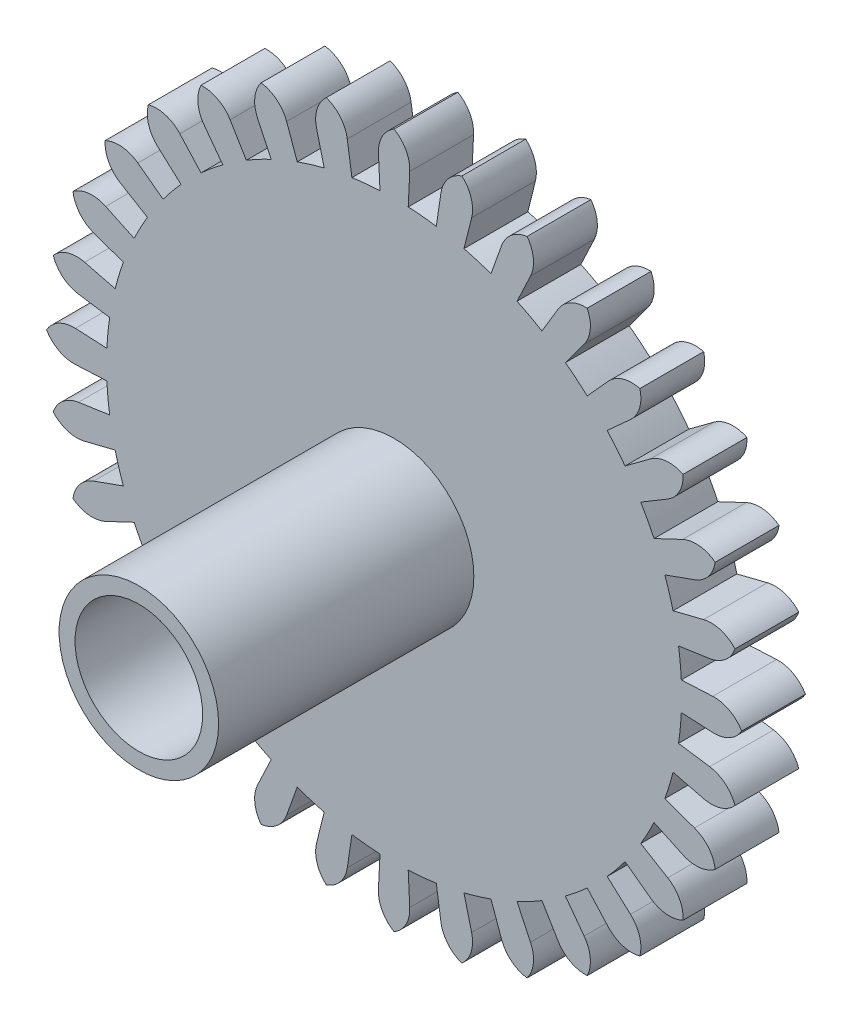
SolidWorks part; units mm, degrees
material "AISI 347 Annealed Stainless Steel (SS)"
ref_plane "Front Plane" through (0, 0, 0) normal (0, 0, 1) x (1, 0, 0)
ref_plane "Top Plane" through (0, 0, 0) normal (0, 1, 0) x (1, 0, 0)
ref_plane "Right Plane" through (0, 0, 0) normal (1, 0, 0) x (0, 0, -1)
sketch "Sketch2" plane through (0, 0, 0) normal (0, 0, 1) x (1, 0, 0)
  line L0 (0, 0) -> (0, 5.2279) construction
  line L1 (-0.1769, 3.6007) -> (-0.1963, 3.9952)
  line L2 (0.1769, 3.6007) -> (0.1963, 3.9952)
  line L3 (0.5289, 3.566) -> (0.5869, 3.9567)
  line L4 (0.876, 3.497) -> (0.9719, 3.8801)
  line L5 (1.2145, 3.3943) -> (1.3475, 3.7662)
  line L6 (1.5414, 3.2589) -> (1.7102, 3.6159)
  line L7 (1.8533, 3.0921) -> (2.0564, 3.4309)
  line L8 (2.1475, 2.8956) -> (2.3828, 3.2128)
  line L9 (2.421, 2.6711) -> (2.6862, 2.9638)
  line L10 (2.6711, 2.421) -> (2.9638, 2.6862)
  line L11 (2.8956, 2.1475) -> (3.2128, 2.3828)
  line L12 (3.0921, 1.8533) -> (3.4309, 2.0564)
  line L13 (3.2589, 1.5414) -> (3.6159, 1.7102)
  line L14 (3.3943, 1.2145) -> (3.7662, 1.3475)
  line L15 (3.497, 0.876) -> (3.8801, 0.9719)
  line L16 (3.566, 0.5289) -> (3.9567, 0.5869)
  line L17 (3.6007, 0.1769) -> (3.9952, 0.1963)
  line L18 (3.6007, -0.1769) -> (3.9952, -0.1963)
  line L19 (3.566, -0.5289) -> (3.9567, -0.5869)
  line L20 (3.497, -0.876) -> (3.8801, -0.9719)
  line L21 (3.3943, -1.2145) -> (3.7662, -1.3475)
  line L22 (3.2589, -1.5414) -> (3.6159, -1.7102)
  line L23 (3.0921, -1.8533) -> (3.4309, -2.0564)
  line L24 (2.8956, -2.1475) -> (3.2128, -2.3828)
  line L25 (2.6711, -2.421) -> (2.9638, -2.6862)
  line L26 (2.421, -2.6711) -> (2.6862, -2.9638)
  line L27 (2.1475, -2.8956) -> (2.3828, -3.2128)
  line L28 (1.8533, -3.0921) -> (2.0564, -3.4309)
  line L29 (1.5414, -3.2589) -> (1.7102, -3.6159)
  line L30 (1.2145, -3.3943) -> (1.3475, -3.7662)
  line L31 (0.876, -3.497) -> (0.9719, -3.8801)
  line L32 (0.5289, -3.566) -> (0.5869, -3.9567)
  line L33 (0.1769, -3.6007) -> (0.1963, -3.9952)
  line L34 (-0.1769, -3.6007) -> (-0.1963, -3.9952)
  line L35 (-0.5289, -3.566) -> (-0.5869, -3.9567)
  line L36 (-0.876, -3.497) -> (-0.9719, -3.8801)
  line L37 (-1.2145, -3.3943) -> (-1.3475, -3.7662)
  line L38 (-1.5414, -3.2589) -> (-1.7102, -3.6159)
  line L39 (-1.8533, -3.0921) -> (-2.0564, -3.4309)
  line L40 (-2.1475, -2.8956) -> (-2.3828, -3.2128)
  line L41 (-2.421, -2.6711) -> (-2.6862, -2.9638)
  line L42 (-2.6711, -2.421) -> (-2.9638, -2.6862)
  line L43 (-2.8956, -2.1475) -> (-3.2128, -2.3828)
  line L44 (-3.0921, -1.8533) -> (-3.4309, -2.0564)
  line L45 (-3.2589, -1.5414) -> (-3.6159, -1.7102)
  line L46 (-3.3943, -1.2145) -> (-3.7662, -1.3475)
  line L47 (-3.497, -0.876) -> (-3.8801, -0.9719)
  line L48 (-3.566, -0.5289) -> (-3.9567, -0.5869)
  line L49 (-3.6007, -0.1769) -> (-3.9952, -0.1963)
  line L50 (-3.6007, 0.1769) -> (-3.9952, 0.1963)
  line L51 (-3.566, 0.5289) -> (-3.9567, 0.5869)
  line L52 (-3.497, 0.876) -> (-3.8801, 0.9719)
  line L53 (-3.3943, 1.2145) -> (-3.7662, 1.3475)
  line L54 (-3.2589, 1.5414) -> (-3.6159, 1.7102)
  line L55 (-3.0921, 1.8533) -> (-3.4309, 2.0564)
  line L56 (-2.8956, 2.1475) -> (-3.2128, 2.3828)
  line L57 (-2.6711, 2.421) -> (-2.9638, 2.6862)
  line L58 (-2.421, 2.6711) -> (-2.6862, 2.9638)
  line L59 (-2.1475, 2.8956) -> (-2.3828, 3.2128)
  line L60 (-1.8533, 3.0921) -> (-2.0564, 3.4309)
  line L61 (-1.5414, 3.2589) -> (-1.7102, 3.6159)
  line L62 (-1.2145, 3.3943) -> (-1.3475, 3.7662)
  line L63 (-0.876, 3.497) -> (-0.9719, 3.8801)
  line L64 (-0.5289, 3.566) -> (-0.5869, 3.9567)
  arc A0 (0.5289, 3.566) -> (0.1769, 3.6007) centre (0, 0) ccw
  arc A1 (-0.1769, 3.6007) -> (-0.5289, 3.566) centre (0, 0) ccw
  arc A2 (1.2145, 3.3943) -> (0.876, 3.497) centre (0, 0) ccw
  arc A3 (0.1963, 3.9952) -> (0, 4.3574) centre (-0.2002, 4.0147) ccw
  arc A4 (-0.1963, 3.9952) -> (0, 4.3574) centre (0.2002, 4.0147) cw
  arc A5 (0.9719, 3.8801) -> (0.8501, 4.2737) centre (0.5869, 3.9766) ccw
  arc A6 (0.5869, 3.9567) -> (0.8501, 4.2737) centre (0.9795, 3.8985) cw
  arc A7 (1.7102, 3.6159) -> (1.6675, 4.0257) centre (1.3514, 3.7857) ccw
  arc A8 (1.3475, 3.7662) -> (1.6675, 4.0257) centre (1.7213, 3.6325) cw
  arc A9 (2.3828, 3.2128) -> (2.4209, 3.6231) centre (2.064, 3.4493) ccw
  arc A10 (2.0564, 3.4309) -> (2.4209, 3.6231) centre (2.3969, 3.2269) cw
  arc A11 (2.9638, 2.6862) -> (3.0812, 3.0812) centre (2.6973, 2.9803) ccw
  arc A12 (2.6862, 2.9638) -> (3.0812, 3.0812) centre (2.9803, 2.6973) cw
  arc A13 (3.4309, 2.0564) -> (3.6231, 2.4209) centre (3.2269, 2.3969) ccw
  arc A14 (3.2128, 2.3828) -> (3.6231, 2.4209) centre (3.4493, 2.064) cw
  arc A15 (3.7662, 1.3475) -> (4.0257, 1.6675) centre (3.6325, 1.7213) ccw
  arc A16 (3.6159, 1.7102) -> (4.0257, 1.6675) centre (3.7857, 1.3514) cw
  arc A17 (3.9567, 0.5869) -> (4.2737, 0.8501) centre (3.8985, 0.9795) ccw
  arc A18 (3.8801, 0.9719) -> (4.2737, 0.8501) centre (3.9766, 0.5869) cw
  arc A19 (3.9952, -0.1963) -> (4.3574, 0) centre (4.0147, 0.2002) ccw
  arc A20 (3.9952, 0.1963) -> (4.3574, 0) centre (4.0147, -0.2002) cw
  arc A21 (3.8801, -0.9719) -> (4.2737, -0.8501) centre (3.9766, -0.5869) ccw
  arc A22 (3.9567, -0.5869) -> (4.2737, -0.8501) centre (3.8985, -0.9795) cw
  arc A23 (3.6159, -1.7102) -> (4.0257, -1.6675) centre (3.7857, -1.3514) ccw
  arc A24 (3.7662, -1.3475) -> (4.0257, -1.6675) centre (3.6325, -1.7213) cw
  arc A25 (3.2128, -2.3828) -> (3.6231, -2.4209) centre (3.4493, -2.064) ccw
  arc A26 (3.4309, -2.0564) -> (3.6231, -2.4209) centre (3.2269, -2.3969) cw
  arc A27 (2.6862, -2.9638) -> (3.0812, -3.0812) centre (2.9803, -2.6973) ccw
  arc A28 (2.9638, -2.6862) -> (3.0812, -3.0812) centre (2.6973, -2.9803) cw
  arc A29 (2.0564, -3.4309) -> (2.4209, -3.6231) centre (2.3969, -3.2269) ccw
  arc A30 (2.3828, -3.2128) -> (2.4209, -3.6231) centre (2.064, -3.4493) cw
  arc A31 (1.3475, -3.7662) -> (1.6675, -4.0257) centre (1.7213, -3.6325) ccw
  arc A32 (1.7102, -3.6159) -> (1.6675, -4.0257) centre (1.3514, -3.7857) cw
  arc A33 (0.5869, -3.9567) -> (0.8501, -4.2737) centre (0.9795, -3.8985) ccw
  arc A34 (0.9719, -3.8801) -> (0.8501, -4.2737) centre (0.5869, -3.9766) cw
  arc A35 (-0.1963, -3.9952) -> (0, -4.3574) centre (0.2002, -4.0147) ccw
  arc A36 (0.1963, -3.9952) -> (0, -4.3574) centre (-0.2002, -4.0147) cw
  arc A37 (-0.9719, -3.8801) -> (-0.8501, -4.2737) centre (-0.5869, -3.9766) ccw
  arc A38 (-0.5869, -3.9567) -> (-0.8501, -4.2737) centre (-0.9795, -3.8985) cw
  arc A39 (-1.7102, -3.6159) -> (-1.6675, -4.0257) centre (-1.3514, -3.7857) ccw
  arc A40 (-1.3475, -3.7662) -> (-1.6675, -4.0257) centre (-1.7213, -3.6325) cw
  arc A41 (-2.3828, -3.2128) -> (-2.4209, -3.6231) centre (-2.064, -3.4493) ccw
  arc A42 (-2.0564, -3.4309) -> (-2.4209, -3.6231) centre (-2.3969, -3.2269) cw
  arc A43 (-2.9638, -2.6862) -> (-3.0812, -3.0812) centre (-2.6973, -2.9803) ccw
  arc A44 (-2.6862, -2.9638) -> (-3.0812, -3.0812) centre (-2.9803, -2.6973) cw
  arc A45 (-3.4309, -2.0564) -> (-3.6231, -2.4209) centre (-3.2269, -2.3969) ccw
  arc A46 (-3.2128, -2.3828) -> (-3.6231, -2.4209) centre (-3.4493, -2.064) cw
  arc A47 (-3.7662, -1.3475) -> (-4.0257, -1.6675) centre (-3.6325, -1.7213) ccw
  arc A48 (-3.6159, -1.7102) -> (-4.0257, -1.6675) centre (-3.7857, -1.3514) cw
  arc A49 (-3.9567, -0.5869) -> (-4.2737, -0.8501) centre (-3.8985, -0.9795) ccw
  arc A50 (-3.8801, -0.9719) -> (-4.2737, -0.8501) centre (-3.9766, -0.5869) cw
  arc A51 (-3.9952, 0.1963) -> (-4.3574, 0) centre (-4.0147, -0.2002) ccw
  arc A52 (-3.9952, -0.1963) -> (-4.3574, 0) centre (-4.0147, 0.2002) cw
  arc A53 (-3.8801, 0.9719) -> (-4.2737, 0.8501) centre (-3.9766, 0.5869) ccw
  arc A54 (-3.9567, 0.5869) -> (-4.2737, 0.8501) centre (-3.8985, 0.9795) cw
  arc A55 (-3.6159, 1.7102) -> (-4.0257, 1.6675) centre (-3.7857, 1.3514) ccw
  arc A56 (-3.7662, 1.3475) -> (-4.0257, 1.6675) centre (-3.6325, 1.7213) cw
  arc A57 (-3.2128, 2.3828) -> (-3.6231, 2.4209) centre (-3.4493, 2.064) ccw
  arc A58 (-3.4309, 2.0564) -> (-3.6231, 2.4209) centre (-3.2269, 2.3969) cw
  arc A59 (-2.6862, 2.9638) -> (-3.0812, 3.0812) centre (-2.9803, 2.6973) ccw
  arc A60 (-2.9638, 2.6862) -> (-3.0812, 3.0812) centre (-2.6973, 2.9803) cw
  arc A61 (-2.0564, 3.4309) -> (-2.4209, 3.6231) centre (-2.3969, 3.2269) ccw
  arc A62 (-2.3828, 3.2128) -> (-2.4209, 3.6231) centre (-2.064, 3.4493) cw
  arc A63 (-1.3475, 3.7662) -> (-1.6675, 4.0257) centre (-1.7213, 3.6325) ccw
  arc A64 (-1.7102, 3.6159) -> (-1.6675, 4.0257) centre (-1.3514, 3.7857) cw
  arc A65 (-0.5869, 3.9567) -> (-0.8501, 4.2737) centre (-0.9795, 3.8985) ccw
  arc A66 (-0.9719, 3.8801) -> (-0.8501, 4.2737) centre (-0.5869, 3.9766) cw
  arc A67 (-0.876, 3.497) -> (-1.2145, 3.3943) centre (0, 0) ccw
  arc A68 (-1.5414, 3.2589) -> (-1.8533, 3.0921) centre (0, 0) ccw
  arc A69 (-2.1475, 2.8956) -> (-2.421, 2.6711) centre (0, 0) ccw
  arc A70 (-2.6711, 2.421) -> (-2.8956, 2.1475) centre (0, 0) ccw
  arc A71 (-3.0921, 1.8533) -> (-3.2589, 1.5414) centre (0, 0) ccw
  arc A72 (1.8533, 3.0921) -> (1.5414, 3.2589) centre (0, 0) ccw
  arc A73 (2.421, 2.6711) -> (2.1475, 2.8956) centre (0, 0) ccw
  arc A74 (2.8956, 2.1475) -> (2.6711, 2.421) centre (0, 0) ccw
  arc A75 (-3.3943, 1.2145) -> (-3.497, 0.876) centre (0, 0) ccw
  arc A76 (-3.566, 0.5289) -> (-3.6007, 0.1769) centre (0, 0) ccw
  arc A77 (-3.6007, -0.1769) -> (-3.566, -0.5289) centre (0, 0) ccw
  arc A78 (-3.497, -0.876) -> (-3.3943, -1.2145) centre (0, 0) ccw
  arc A79 (-3.2589, -1.5414) -> (-3.0921, -1.8533) centre (0, 0) ccw
  arc A80 (-2.8956, -2.1475) -> (-2.6711, -2.421) centre (0, 0) ccw
  arc A81 (-2.421, -2.6711) -> (-2.1475, -2.8956) centre (0, 0) ccw
  arc A82 (-1.8533, -3.0921) -> (-1.5414, -3.2589) centre (0, 0) ccw
  arc A83 (-1.2145, -3.3943) -> (-0.876, -3.497) centre (0, 0) ccw
  arc A84 (-0.5289, -3.566) -> (-0.1769, -3.6007) centre (0, 0) ccw
  arc A85 (0.1769, -3.6007) -> (0.5289, -3.566) centre (0, 0) ccw
  arc A86 (0.876, -3.497) -> (1.2145, -3.3943) centre (0, 0) ccw
  arc A87 (1.5414, -3.2589) -> (1.8533, -3.0921) centre (0, 0) ccw
  arc A88 (2.1475, -2.8956) -> (2.421, -2.6711) centre (0, 0) ccw
  arc A89 (2.6711, -2.421) -> (2.8956, -2.1475) centre (0, 0) ccw
  arc A90 (3.0921, -1.8533) -> (3.2589, -1.5414) centre (0, 0) ccw
  arc A91 (3.3943, -1.2145) -> (3.497, -0.876) centre (0, 0) ccw
  arc A92 (3.566, -0.5289) -> (3.6007, -0.1769) centre (0, 0) ccw
  arc A93 (3.6007, 0.1769) -> (3.566, 0.5289) centre (0, 0) ccw
  arc A94 (3.497, 0.876) -> (3.3943, 1.2145) centre (0, 0) ccw
  arc A95 (3.2589, 1.5414) -> (3.0921, 1.8533) centre (0, 0) ccw
  circle A96 centre (0, 0) radius 0.8
  circle A97 centre (0, 0) radius 1
  point P232 (0, 0)
  dimension "D1" = 1.6
  dimension "D2" = 7.21
  dimension "D3" = 2
  dimension "D4" = 32
extrude "Boss-Extrude1" add sketch "Sketch2" along normal blind 0.8 contours A97 A4 L1 A1 L64 A65 A66 L63 A67 L62 A63 A64 L61 A68 L60 A61 A62 L59 A69 L58 A59 A60 L57 A70 L56 A57 A58 L55 A71 L54 A55 A56 L53 A75 L52 A53 A54 L51 A76 L50 A51 A52 L49 A77 L48 A49 A50 L47 A78 L46 region at (-0.0635, 3.804, 0)
extrude "Boss-Extrude2" add sketch "Sketch2<3>" along normal blind 4 contours A96 A97 region at (-0.9717, 0, 0)
sketch "Sketch2<3>" plane through (0, 0, 0) normal (0, 0, 1) x (1, 0, 0) same geometry as "Sketch2"
